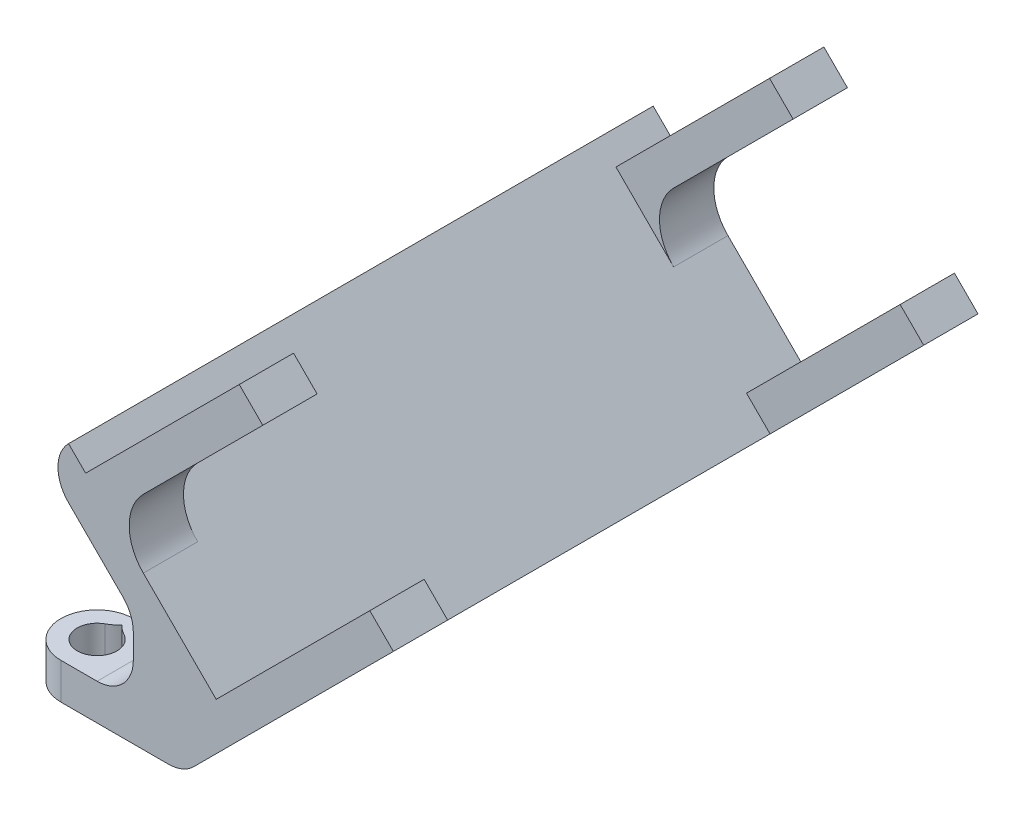
SolidWorks part; units mm, degrees
ref_plane "Front Plane" through (0, 0, 0) normal (0, 0, 1) x (1, 0, 0)
ref_plane "Top Plane" through (0, 0, 0) normal (0, 1, 0) x (1, 0, 0)
ref_plane "Right Plane" through (0, 0, 0) normal (1, 0, 0) x (0, 0, -1)
sketch "Sketch1" plane through (0, 0, 0) normal (0, 1, 0) x (1, 0, 0)
  line L0 (0, 18.22) -> (0, -18.22)
  line L1 (0, 0) -> (13.5344, 0) construction
  line L2 (0, 24.22) -> (3, 24.22)
  line L3 (0, 22.67) -> (0, 22.87) construction
  line L4 (0, -19.57) -> (0, -19.17) construction
  line L5 (0, -19.57) -> (0, -19.77) construction
  line L6 (0, -19.77) -> (0.7874, -19.77) construction
  line L7 (3, 24.22) -> (3, -24.22)
  line L8 (3, -24.22) -> (0, -24.22)
  line L9 (0, 22.87) -> (0, 23.27) construction
  line L10 (0, 22.67) -> (0.7874, 22.67) construction
  circle A0 centre (0, 21.22) radius 1.65
  circle A1 centre (0, -21.22) radius 1.65
  arc A2 (0, 24.22) -> (-2, 18.9839) centre (0, 21.22) ccw
  arc A3 (-2, -18.9839) -> (0, -24.22) centre (0, -21.22) ccw
  arc A4 (0, 24.22) -> (0, 18.22) centre (0, 21.22) ccw
  arc A5 (0, -18.22) -> (0, -24.22) centre (0, -21.22) ccw
  arc A6 (0.7874, -19.77) -> (0, -19.17) centre (2.3307, -16.928) cw
  arc A7 (-0.7874, -19.77) -> (0, -19.17) centre (-2.3307, -16.928) ccw
  arc A8 (0.7874, 22.67) -> (0, 23.27) centre (2.3307, 25.512) cw
  arc A9 (-0.7874, 22.67) -> (0, 23.27) centre (-2.3307, 25.512) ccw
  dimension "D2" = 3.3
  dimension "D3" = 6
  dimension "D5" = 0.4
  dimension "D1" = 42.44
  dimension "D4" = 3
  dimension "D6" = 0.2
  dimension "D7" = 0.4
  dimension "D8" = 0.2
extrude "Boss-Extrude1" add sketch "Sketch1" along normal blind 3 contours A3 A1 | A3 A2 region at (1.166, 0, 0.0047)
sketch "Sketch2" plane through (0, 0, 0) normal (0, 0, 1) x (1, 0, 0)
  line L0 (3, 0) -> (9, 0)
  line L1 (9, 0) -> (9, 6.2574)
  line L2 (9, 6.2574) -> (6, 6.2574)
  line L3 (6, 6.2574) -> (6, 3)
  line L4 (6, 3) -> (3, 3)
  line L5 (0, 3) -> (3, 3) construction
  line L6 (6, 6.2574) -> (6, 13.5)
  line L7 (1.8787, 17.6213) -> (14.8187, 4.6813)
  line L8 (14.8187, 4.6813) -> (12.6974, 2.5599)
  line L9 (12.6974, 2.5599) -> (-0.2426, 15.5)
  line L10 (-0.2426, 15.5) -> (1.8787, 17.6213)
  line L11 (3, 3) -> (3, 0) construction
  line L12 (4, 15.5) -> (16.7279, 28.2279)
  line L13 (16.7279, 28.2279) -> (18.1421, 26.8137)
  line L14 (18.1421, 26.8137) -> (5.4142, 14.0858)
  line L15 (12.6974, 2.5599) -> (14.1116, 1.1457)
  line L16 (14.1116, 1.1457) -> (28.9609, 15.995)
  line L17 (28.9609, 15.995) -> (27.5467, 17.4092)
  line L18 (27.5467, 17.4092) -> (14.8187, 4.6813)
  line L19 (3, 3) -> (3, 0)
  line L20 (4, 15.5) -> (16.7279, 28.2279)
  line L21 (9, 0) -> (12.9659, 0)
  line L22 (12.9659, 0) -> (14.1116, 1.1457)
  line L23 (4, 15.5) -> (2.0484, 17.4516)
  line L24 (16.7279, 28.2279) -> (14.7763, 30.1795)
  line L25 (2.0484, 17.4516) -> (14.7763, 30.1795)
  line L26 (14.8187, 4.6813) -> (27.5467, 17.4092)
  line L27 (14.8187, 4.6813) -> (12.8671, 6.6329)
  line L28 (27.5467, 17.4092) -> (25.595, 19.3608)
  line L29 (12.8671, 6.6329) -> (25.595, 19.3608)
  line L30 (12.6974, 2.5599) -> (10.1375, 0)
  line L31 (-0.2426, 15.5) -> (-1.4871, 16.7445)
  line L32 (-0.2426, 15.5) -> (1.8787, 17.6213)
  line L33 (-1.4871, 16.7445) -> (0.6342, 18.8658)
  line L34 (1.8787, 17.6213) -> (0.6342, 18.8658)
  dimension "D1" = 3
  dimension "D2" = 13.5
  dimension "D3" = 45
  dimension "D4" = 6
  dimension "D5" = 2
  dimension "D6" = 2
  dimension "D7" = 18
  dimension "D8" = 15.3
  dimension "D9" = 3
  dimension "D10" = 2.76
  dimension "D11" = 2
extrude "Boss-Extrude2" add sketch "Sketch2" against normal up to vertex (24.22 mm away) and the other way up to vertex (24.22 mm away) contours L4 L19 L0 L1 L2 L3 | L2 L9 L6 | L9 L8 L7 L6 | L10 L9 L6 L7 | L15 L9 L1 | L25 L7 L12 L24 | L29 L7 L18 L28 | L10 L34 L33 L31 region at (6.5278, 2.6009, 0) region at (10.2749, 2.7059, 0) region at (9.9032, 7.5721, 0) region at (7, 7.2574, 0) region at (3.3728, 13.8611, 0) region at (20.2069, 12.021, 0) region at (0.1958, 17.1829, 0) region at (9.3882, 22.8398, 0) up to point (3, 3, -24.22) other way up to point (3, 3, 24.22)
sketch "Sketch4" plane through (-7.7016, 7.7016, 0) normal (-0.7071, 0.7071, 0) x (0, 0, 1)
  line L0 (-19.72, 31.7886) -> (19.72, 31.7886)
  line L1 (-19.72, 31.7886) -> (-19.72, 13.7886)
  line L2 (19.72, 31.7886) -> (19.72, 13.7886)
  line L3 (-19.72, 13.7886) -> (19.72, 13.7886)
  line L6 (-24.22, 13.7886) -> (-24.22, 31.7886) construction
  line L7 (24.22, 13.7886) -> (24.22, 31.7886) construction
  line L8 (-24.22, 13.7886) -> (24.22, 13.7886) construction
  line L9 (-24.22, 31.7886) -> (24.22, 31.7886) construction
  dimension "D1" = 4.5
  dimension "D2" = 4.5
extrude "Cut-Extrude2" cut sketch "Sketch4" against normal through all
fillet "Fillet1" radius 3 2 edges at (6, 3, 0) (6, 9.2574, 0)
fillet "Fillet2" radius 3 2 edges at (-1.4871, 16.7445, 0) (10.1375, 0, 0)
fillet "Fillet3" radius 4 2 edges at (4, 15.5, -21.97) (4, 15.5, 21.97)
